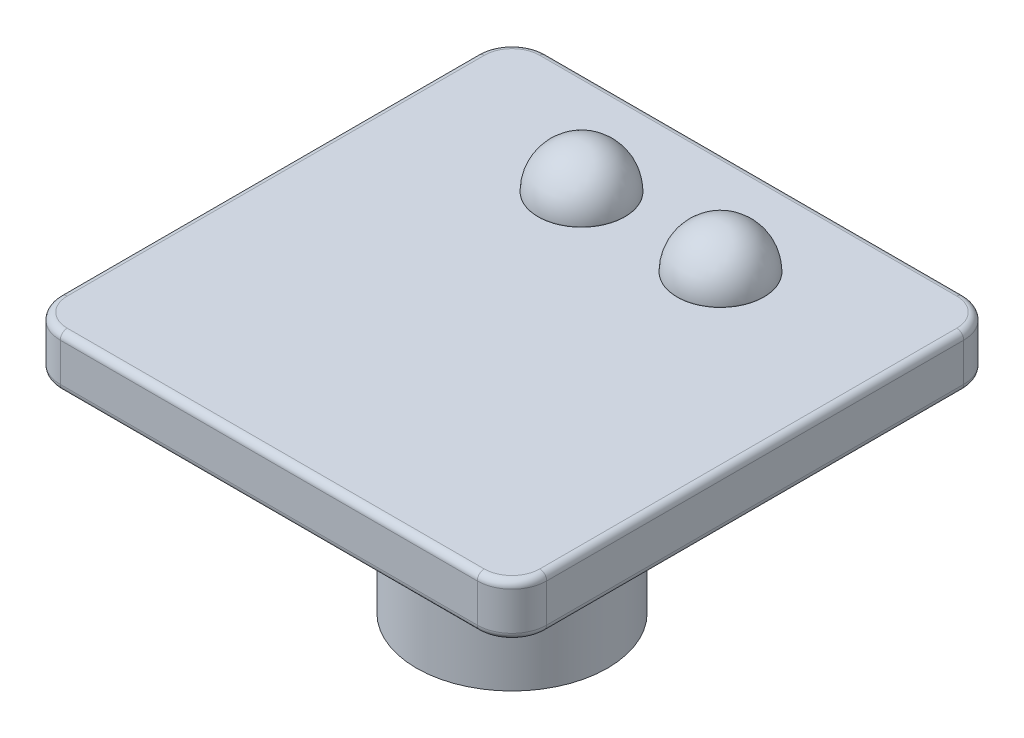
SolidWorks part; units mm, degrees
ref_plane "Front Plane" through (0, 0, 0) normal (0, 0, 1) x (1, 0, 0)
ref_plane "Top Plane" through (0, 0, 0) normal (0, 1, 0) x (1, 0, 0)
ref_plane "Right Plane" through (0, 0, 0) normal (1, 0, 0) x (0, 0, -1)
sketch "Sketch1" plane through (0, 0, 0) normal (0, 1, 0) x (1, 0, 0)
  line L1 (-7.3247, 4.3967) -> (4.6753, 4.3967)
  line L2 (-8.3247, 3.3967) -> (-8.3247, -8.6033)
  line L3 (-7.3247, -9.6033) -> (4.6753, -9.6033)
  line L4 (5.6753, 3.3967) -> (5.6753, -8.6033)
  arc A0 (-8.3247, -8.6033) -> (-7.3247, -9.6033) centre (-7.3247, -8.6033) ccw
  arc A1 (4.6753, -9.6033) -> (5.6753, -8.6033) centre (4.6753, -8.6033) ccw
  arc A2 (4.6753, 4.3967) -> (5.6753, 3.3967) centre (4.6753, 3.3967) cw
  arc A3 (-7.3247, 4.3967) -> (-8.3247, 3.3967) centre (-7.3247, 3.3967) ccw
  point P8 (5.6753, -9.6033)
  point P11 (5.6753, 4.3967)
  point P14 (-8.3247, 4.3967)
  dimension "D3" = 1
  dimension "D1" = 14
  dimension "D2" = 14
extrude "Boss-Extrude1" add sketch "Sketch1" along normal blind 1.5
sketch "Sketch2" plane through (0, 0, 0) normal (0, -1, 0) x (1, 0, 0)
  line L0 (-7.3247, 9.6033) -> (4.6753, 9.6033) construction
  line L1 (5.6753, 8.6033) -> (5.6753, -3.3967) construction
  line L2 (-1.3247, -4.3967) -> (-1.3247, 9.6033) construction
  line L3 (-8.3247, 2.6033) -> (5.6753, 2.6033) construction
  line L4 (-8.3247, -3.3967) -> (-8.3247, 8.6033) construction
  circle A0 centre (-1.3247, 2.6033) radius 2.75
  dimension "D1" = 7
  dimension "D2" = 7
extrude "Boss-Extrude2" add sketch "Sketch2" along normal blind 6
sketch "Sketch3" plane through (0, -6, 0) normal (0, -1, 0) x (1, 0, 0)
  line L0 (-1.3247, 5.3533) -> (-1.3247, -0.1467) construction
  line L1 (-3.3247, 3.1533) -> (0.6753, 3.1533)
  line L2 (-3.3247, 3.1533) -> (-3.3247, 2.0533)
  line L3 (-3.3247, 2.0533) -> (0.6753, 2.0533)
  line L4 (0.6753, 3.1533) -> (0.6753, 2.0533)
  line L5 (-1.8747, 4.6033) -> (-0.7747, 4.6033)
  line L6 (-1.8747, 4.6033) -> (-1.8747, 0.6033)
  line L7 (-1.8747, 0.6033) -> (-0.7747, 0.6033)
  line L8 (-0.7747, 4.6033) -> (-0.7747, 0.6033)
  line L9 (-4.0747, 2.6033) -> (1.4253, 2.6033) construction
  circle A3 centre (-1.3247, 2.6033) radius 2.75 construction
  circle A4 centre (-1.3247, 2.6033) radius 2.75 construction
  dimension "D7" = 0.55
  dimension "D1" = 4
  dimension "D2" = 1.1
  dimension "D3" = 1.1
  dimension "D4" = 4
  dimension "D5" = 2
  dimension "D6" = 2
  dimension "D8" = 0.55
extrude "Cut-Extrude1" cut sketch "Sketch3" against normal blind 6 contours L8 L5 L6 L1 | L1 L8 L3 L4 | L8 L1 L6 L3 | L6 L1 L2 L3 | L8 L3 L6 L7 region at (-2.5997, -6, 2.6033) region at (-1.3247, -6, 3.8783) region at (-1.3247, -6, 2.6033) region at (-0.0497, -6, 2.6033) region at (-1.3247, -6, 1.3283)
chamfer "Chamfer1" distance 0.3 angle 45 12 edges at (-1.3247, -6, 0.6033) (-1.8747, -6, 1.3283) (-2.5997, -6, 2.0533) (-3.3247, -6, 2.6033) (-2.5997, -6, 3.1533) (-0.7747, -6, 1.3283) (-0.0497, -6, 2.0533) (0.6753, -6, 2.6033) (-0.0497, -6, 3.1533) (-0.7747, -6, 3.8783) (-1.3247, -6, 4.6033) (-1.8747, -6, 3.8783)
fillet "Fillet1" radius 1 1 edges at (-1.3247, 0, -0.1467)
sketch "Sketch4" plane through (0, 1.5, 0) normal (0, 1, 0) x (1, 0, 0)
  line L0 (-1.3247, 4.3967) -> (-1.3247, -9.6033) construction
  line L1 (4.6753, 4.3967) -> (-7.3247, 4.3967) construction
  line L2 (-7.3247, -9.6033) -> (4.6753, -9.6033) construction
  line L3 (5.6753, -2.6033) -> (-8.3247, -2.6033) construction
  line L4 (-8.3247, 3.3967) -> (-8.3247, -8.6033) construction
  line L5 (5.6753, -8.6033) -> (5.6753, 3.3967) construction
  line L6 (-3.3247, 4.3967) -> (-3.3247, -9.6033) construction
  line L7 (0.6753, 4.3967) -> (0.6753, -9.6033) construction
  line L8 (-8.3247, 1.3967) -> (5.6753, 1.3967) construction
  line L9 (5.6753, -6.6033) -> (-8.3247, -6.6033) construction
  circle A0 centre (-3.3247, 1.3967) radius 1.25
  circle A5 centre (0.6753, 1.3967) radius 1.25
  dimension "D1" = 4
  dimension "D2" = 4
  dimension "D3" = 2
  dimension "D4" = 2
extrude "Boss-Extrude3" add sketch "Sketch4" along normal blind 0.01
dome "Dome1" faces to dome 1 distance 1.25 reverse direction no elliptical dome no face at (-3.3247, 1.51, -0.1467) parameters "D1"=1.25
dome "Dome2" faces to dome 1 distance 1.25 reverse direction no elliptical dome no face at (0.6753, 1.51, -0.1467) parameters "D1"=1.25
fillet "Fillet3" radius 0.2 16 edges at (5.3824, 1.5, -4.1038) (5.6753, 1.5, 2.6033) (5.3824, 1.5, 9.3104) (-1.3247, 1.5, 9.6033) (-8.0318, 1.5, 9.3104) (-8.0318, 1.5, -4.1038) (-8.3247, 1.5, 2.6033) (-1.3247, 1.5, -4.3967) (5.3824, 0, 9.3104) (5.6753, 0, 2.6033) (5.3824, 0, -4.1038) (-1.3247, 0, -4.3967) (-8.0318, 0, -4.1038) (-8.3247, 0, 2.6033) (-8.0318, 0, 9.3104) (-1.3247, 0, 9.6033)
